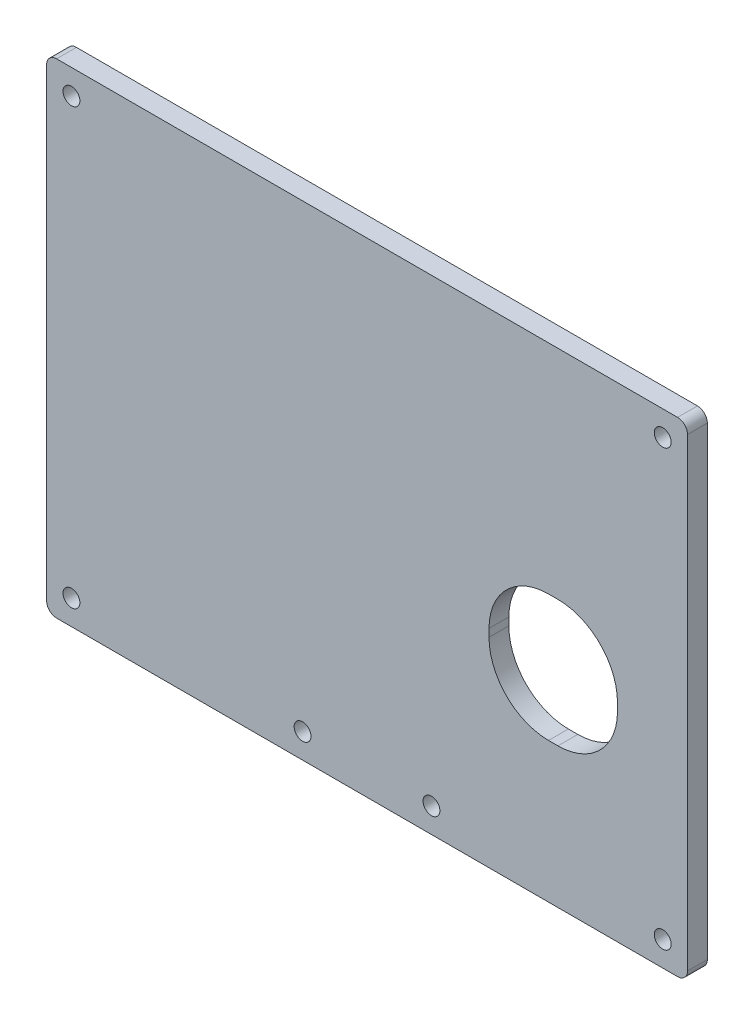
SolidWorks part; units mm, degrees
ref_plane "Front Plane" through (0, 0, 0) normal (0, 0, 1) x (1, 0, 0)
ref_plane "Top Plane" through (0, 0, 0) normal (0, 1, 0) x (1, 0, 0)
ref_plane "Right Plane" through (0, 0, 0) normal (1, 0, 0) x (0, 0, -1)
sketch "Sketch1" plane through (0, 0, 0) normal (0, 0, 1) x (1, 0, 0)
  line L27 (-118.5774, 31.7875) -> (6.5856, 31.7875)
  line L28 (8.5856, 33.7875) -> (8.5856, 127.4077)
  line L29 (6.5856, 129.4077) -> (-118.5774, 129.4077)
  line L30 (-120.5774, 127.4077) -> (-120.5774, 33.7875)
  arc A46 (6.5856, 31.7875) -> (8.5856, 33.7875) centre (6.5856, 33.7875) ccw
  arc A47 (8.5856, 127.4077) -> (6.5856, 129.4077) centre (6.5856, 127.4077) ccw
  arc A48 (-118.5774, 129.4077) -> (-120.5774, 127.4077) centre (-118.5774, 127.4077) ccw
  arc A49 (-120.5774, 33.7875) -> (-118.5774, 31.7875) centre (-118.5774, 33.7875) ccw
extrude "Boss-Extrude1" add sketch "Sketch1" along normal blind 4
hole_wizard "M3 Clearance Hole1" positions "Sketch3" profile "Sketch2" hole size "M3" standard "ISO" end condition through all
sketch "Sketch3" plane through (0, 0, 4) normal (0, 0, 1) x (1, 0, 0)
  point P0 (-115.5774, 124.4077)
  point P2 (3.5856, 124.4077)
  point P4 (-115.5774, 36.7875)
  point P6 (-68.9959, 36.7875)
  point P8 (-43.0153, 36.7875)
  point P10 (3.5856, 36.7875)
sketch "Sketch2" plane through (-115.5774, 124.4077, 4) normal (1, 0, 0) x (0, -1, 0)
  line L0 (0, 0) -> (0, 4)
  line L1 (0, 4) -> (1.7, 4)
  line L2 (1.7, 4) -> (1.7, 0)
  line L5 (1.7, 0) -> (0, 0)
  line L11 (0, -6.35) -> (0, 107.95) construction
  dimension "Thru Hole Dia." = 3.4
  dimension "Thru Hole Depth" = 4
sketch "Sketch4" plane through (0, 0, 4) normal (0, 0, 1) x (1, 0, 0)
  line L1 (-5.5262, 60.0149) -> (-31.4193, 60.0149)
  line L2 (-5.5262, 60.0149) -> (-5.5262, 85.5714)
  line L3 (-5.5262, 85.5714) -> (-31.4193, 85.5714)
  line L4 (-31.4193, 60.0149) -> (-31.4193, 85.5714)
extrude "Cut-Extrude1" cut sketch "Sketch4" against normal blind 8
fillet "Fillet1" radius 12 4 edges at (-5.5262, 85.5714, 2) (-5.5262, 60.0149, 2) (-31.4193, 60.0149, 2) (-31.4193, 85.5714, 2)
